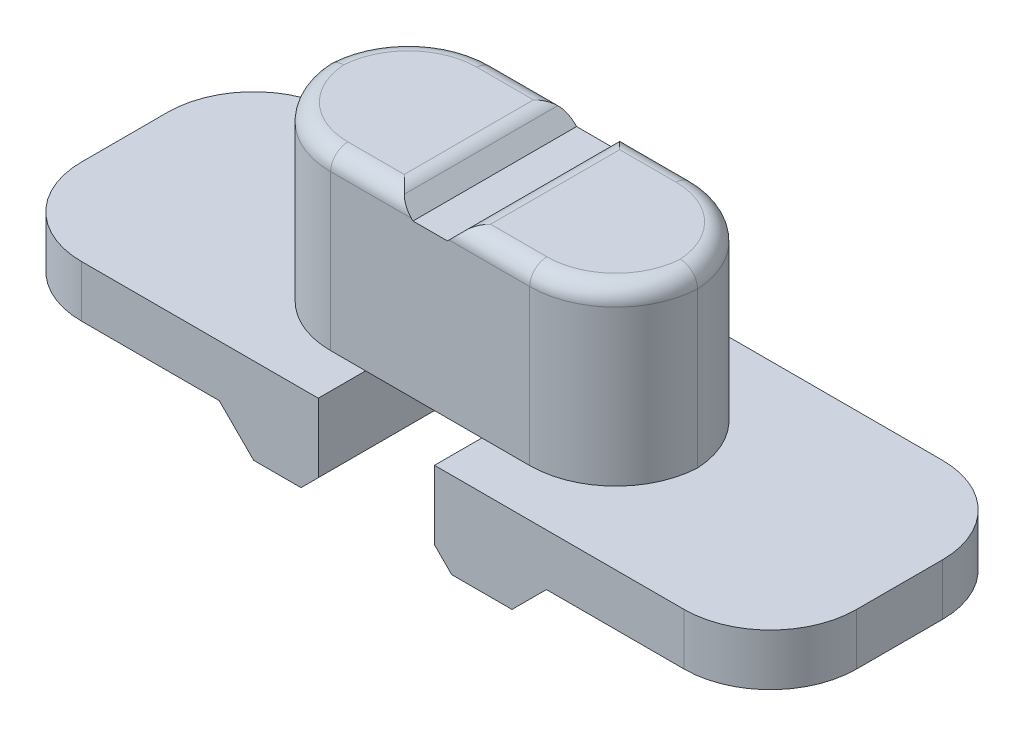
SolidWorks part; units mm, degrees
ref_plane "前视基准面" through (0, 0, 0) normal (0, 0, 1) x (1, 0, 0)
ref_plane "上视基准面" through (0, 0, 0) normal (0, 1, 0) x (1, 0, 0)
ref_plane "右视基准面" through (0, 0, 0) normal (1, 0, 0) x (0, 0, -1)
sketch "草图1" plane through (0, 0, 0) normal (0, 1, 0) x (1, 0, 0)
  line L1 (-4.0252, 1.9436) -> (4.9748, 1.9436)
  line L2 (-4.0252, 1.9436) -> (-4.0252, -1.0564)
  line L3 (-4.0252, -1.0564) -> (4.9748, -1.0564)
  line L4 (4.9748, 1.9436) -> (4.9748, -1.0564)
  line L5 (-4.0252, 1.9436) -> (4.9748, -1.0564) construction
  line L6 (-4.0252, -1.0564) -> (4.9748, 1.9436) construction
  point P0 (0.4748, 0.4436)
  dimension "D1" = 9
  dimension "D2" = 3
extrude "凸台-拉伸1" add sketch "草图1" along normal blind 0.6
sketch "草图2" plane through (0, 0.6, 0) normal (0, 1, 0) x (1, 0, 0)
  line L1 (-1.681, 1.3936) -> (2.6305, 1.3936)
  line L2 (-1.681, 1.3936) -> (-1.681, -0.5064)
  line L3 (-1.681, -0.5064) -> (2.6305, -0.5064)
  line L4 (2.6305, 1.3936) -> (2.6305, -0.5064)
  line L5 (-1.681, 1.3936) -> (2.6305, -0.5064) construction
  line L6 (-1.681, -0.5064) -> (2.6305, 1.3936) construction
  line L7 (4.9748, -1.0564) -> (4.9748, 1.9436) construction
  line L8 (4.9748, 1.9436) -> (-4.0252, 1.9436) construction
  point P0 (0.4748, 0.4436)
  point P5 (0, 0)
  point P6 (0, 0)
  point P9 (0, 0)
  point P12 (4.9748, 0.4436)
  point P13 (0, 0)
  point P14 (-0.5335, 0.4436)
  point P15 (0, 0)
  point P16 (0, 0)
  point P17 (0.4748, 1.9436)
  dimension "D1" = 1.9
extrude "凸台-拉伸2" add sketch "草图2" along normal blind 2
fillet "圆角1" radius 1 8 edges at (-4.0252, 0.3, 1.0564) (-1.681, 1.6, 0.5064) (4.9748, 0.3, 1.0564) (2.6305, 1.6, 0.5064) (-1.681, 1.6, -1.3936) (2.6305, 1.6, -1.3936) (4.9748, 0.3, -1.9436) (-4.0252, 0.3, -1.9436)
sketch "草图3" plane through (0, 0, 0) normal (0, -1, 0) x (1, 0, 0)
  line L0 (3.9748, -1.9436) -> (-3.0252, -1.9436) construction
  line L1 (1.9748, -1.9436) -> (-1.0252, -1.9436)
  line L2 (1.9748, -1.9436) -> (1.9748, 1.0564)
  line L3 (1.9748, 1.0564) -> (-1.0252, 1.0564)
  line L4 (-1.0252, -1.9436) -> (-1.0252, 1.0564)
  line L5 (-3.0252, 1.0564) -> (3.9748, 1.0564) construction
  line L6 (4.9748, 0.0564) -> (4.9748, -0.9436) construction
  point P4 (0, 0)
  point P7 (0, 0)
  point P10 (0, 0)
  point P13 (-0.7108, -2.7168)
  dimension "D1" = 3
  dimension "D2" = 3
extrude "凸台-拉伸3" add sketch "草图3" along normal blind 0.4
chamfer "倒角1" distance 0.4 angle 45 2 edges at (1.9748, 0, -0.4436) (-1.0252, 0, -0.4436)
sketch "草图5" plane through (0, 0, -1.9436) normal (0, 0, -1) x (-1, 0, 0)
  line L1 (0.2752, -0.4) -> (-1.0748, -0.4)
  line L2 (0.2752, -0.4) -> (0.2752, 0.6)
  line L3 (0.2752, 0.6) -> (-1.0748, 0.6)
  line L4 (-1.0748, -0.4) -> (-1.0748, 0.6)
  line L5 (-4.9748, 0) -> (-4.9748, 0.6) construction
  line L6 (1.0252, -0.4) -> (-1.9748, -0.4) construction
  point P4 (0, 0)
  dimension "D1" = 1.35
  dimension "D2" = 3.9
  dimension "D3" = 1
extrude "切除-拉伸1" cut sketch "草图5" against normal up to next
chamfer "倒角2" distance 0.2 angle 45 2 edges at (1.0748, -0.4, -0.4436) (-0.2752, -0.4, -0.4436)
sketch "草图7" plane through (0, 0, 0.5064) normal (0, 0, 1) x (1, 0, 0)
  line L1 (0.9748, 2.3818) -> (-0.0252, 2.3818)
  line L2 (0.9748, 2.3818) -> (0.9748, 2.8182)
  line L3 (0.9748, 2.8182) -> (-0.0252, 2.8182)
  line L4 (-0.0252, 2.3818) -> (-0.0252, 2.8182)
  line L5 (0.9748, 2.3818) -> (-0.0252, 2.8182) construction
  line L6 (0.9748, 2.8182) -> (-0.0252, 2.3818) construction
  point P0 (0.4748, 2.6)
  point P5 (0, 0)
  dimension "D1" = 1
extrude "切除-拉伸2" cut sketch "草图7" against normal up to next and the other way through all
chamfer "倒角3" distance 0.3 angle 45 2 edges at (0.9748, 2.3818, -0.4436) (-0.0252, 2.3818, -0.4436)
fillet "圆角2" radius 0.2 10 edges at (-1.3702, 2.6, 0.2309) (-1.3702, 2.6, -1.1182) (-0.3122, 2.6, -1.3936) (0.0566, 2.6, -0.4436) (-0.3122, 2.6, 0.5064) (2.3197, 2.6, -1.1182) (2.3197, 2.6, 0.2309) (1.2617, 2.6, 0.5064) (0.8929, 2.6, -0.4436) (1.2617, 2.6, -1.3936)
